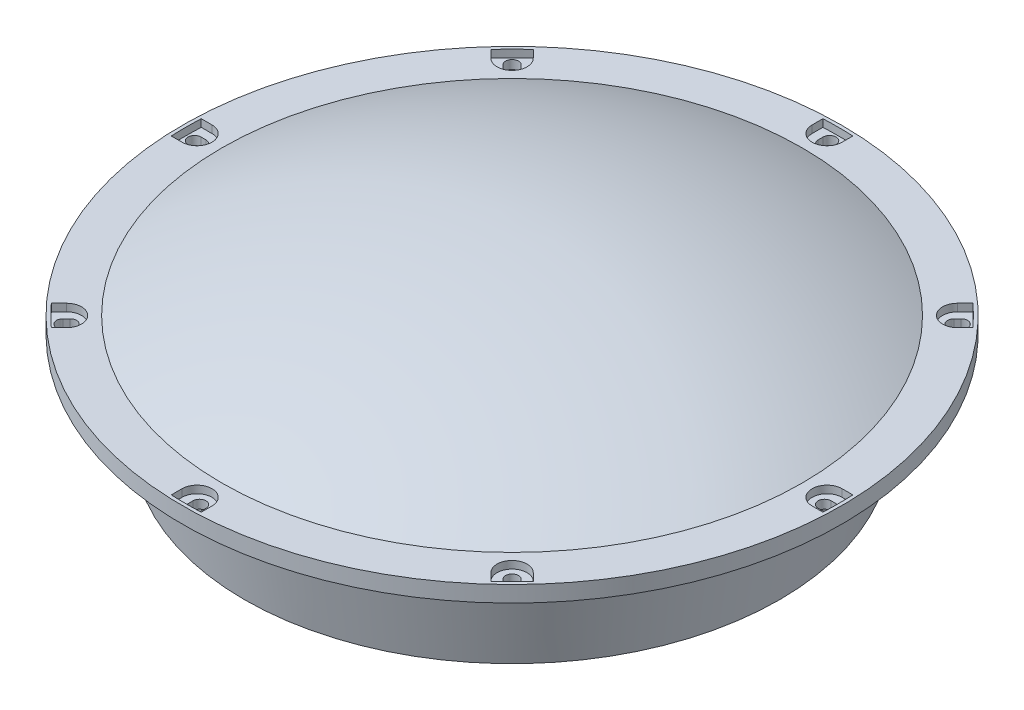
SolidWorks part; units mm, degrees
ref_plane "Front Plane" through (0, 0, 0) normal (0, 0, 1) x (1, 0, 0)
ref_plane "Top Plane" through (0, 0, 0) normal (0, 1, 0) x (1, 0, 0)
ref_plane "Right Plane" through (0, 0, 0) normal (1, 0, 0) x (0, 0, -1)
sketch "Sketch1" plane through (0, 0, 0) normal (0, 0, 1) x (1, 0, 0)
  line L0 (0, 0) -> (0, 73.7) construction
  line L1 (116.25, 45) -> (132, 45)
  line L2 (132, 45) -> (132, 38.55)
  line L3 (132, 38.55) -> (114, 38.55)
  line L4 (114, 38.55) -> (107.2026, 0)
  line L5 (107.2026, 0) -> (0, 0)
  line L6 (0, 0) -> (0, 73.7)
  arc A0 (0, 73.7) -> (116.25, 45) centre (0, -176.0866) cw
  point P5 (111.6329, 45)
  point P7 (132, 42.3972)
  point P12 (0, 0)
  point P13 (0, 0)
  point P14 (0, 0)
  point P15 (78.7048, 40.5816)
  point P16 (102.6235, 43.5993)
  point P17 (83.5332, 42.3922)
  point P18 (132, 56.3313)
  point P19 (79.9742, 56.4746)
  point P20 (132, 52.4645)
  point P21 (116.2083, 47.595)
  point P22 (103.8916, 52.8941)
  dimension "D1" = 228
  dimension "D2" = 264
  dimension "D3" = 45
  dimension "D4" = 73.7
  dimension "D5" = 6.45
  dimension "D6" = 15.75
  dimension "D7" = 80
revolve "Revolve1" add sketch "Sketch1" angle 360 about L0
sketch "Sketch2" plane through (0, 45, 0) normal (0, 1, 0) x (1, 0, 0)
  line L0 (130.4921, 6) -> (120.18, 6)
  line L1 (120.18, 6) -> (120.18, -6)
  line L2 (120.18, -6) -> (130.4921, -6)
  line L3 (120.18, 0) -> (0, 0) construction
  arc A1 (130.4921, -6) -> (130.4921, 6) centre (0, 0) ccw
  circle A2 centre (0, 0) radius 132 construction
  point P3 (131.0464, -6.1093)
  dimension "D3" = 1.37
  dimension "D1" = 12
  dimension "D2" = 10.45
extrude "Cut-Extrude1" cut sketch "Sketch2" against normal blind 3
fillet "Fillet1" 2 edges at (120.18, 43.5, -6) (120.18, 43.5, 6) type full round first side face at (125.3361, 43.5, -6) second side face at (125.3361, 43.5, 6) middle face at (120.18, 43.5, 0)
sketch "Sketch3" plane through (0, 42, 0) normal (0, 1, 0) x (1, 0, 0)
  line L3 (125.18, 0) -> (127.18, 0) construction
  line L4 (125.18, 2.6) -> (127.18, 2.6)
  line L5 (125.18, -2.6) -> (127.18, -2.6)
  arc A2 (125.18, 2.6) -> (125.18, -2.6) centre (125.18, 0) ccw
  arc A3 (127.18, -2.6) -> (127.18, 2.6) centre (127.18, 0) ccw
  point P0 (127.55, 0)
  point P8 (126.18, 0)
  dimension "D1" = 5.2
  dimension "D2" = 7.2
extrude "Cut-Extrude2" cut sketch "Sketch3" against normal through all
pattern_circular "CirPattern2" count 8 over 360 about axis through (0, 0, 0) along (0, -1, 0) of "Cut-Extrude2", "Fillet1", "Cut-Extrude1"
